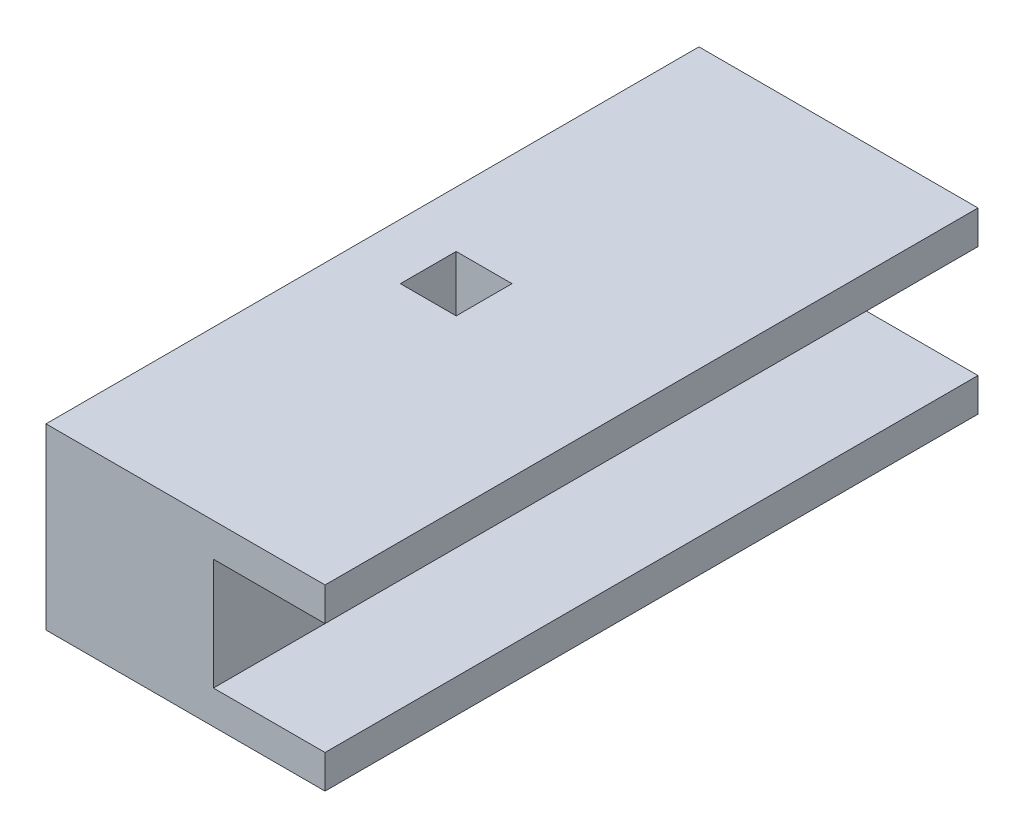
SolidWorks part; units mm, degrees
ref_plane "Płaszczyzna przednia" through (0, 0, 0) normal (0, 0, 1) x (1, 0, 0)
ref_plane "Płaszczyzna górna" through (0, 0, 0) normal (0, 1, 0) x (1, 0, 0)
ref_plane "Płaszczyzna prawa" through (0, 0, 0) normal (1, 0, 0) x (0, 0, -1)
sketch "Szkic1" plane through (0, 0, 0) normal (0, 0, 1) x (1, 0, 0)
  line L0 (10, -10) -> (10, -16)
  line L1 (10, -10) -> (-10, -10)
  line L2 (10, -10) -> (10, 10)
  line L3 (10, 10) -> (-10, 10)
  line L4 (-10, -10) -> (-10, 10)
  line L5 (10, -10) -> (-10, 10) construction
  line L6 (10, 10) -> (-10, -10) construction
  line L7 (10, -16) -> (-40, -16)
  line L8 (-40, -16) -> (-40, 16)
  line L9 (-40, 16) -> (10, 16)
  line L10 (10, 16) -> (10, 10)
  point P0 (0, 0)
  dimension "D1" = 20
  dimension "D2" = 50
  dimension "D3" = 32
  dimension "D4" = 6
extrude "Dodanie-wyciągnięcie1" add sketch "Szkic1" along normal blind 117 contours L10 L9 L8 L7 L0 L1 L4 L3 region at (-20, 0, 0)
sketch "Szkic2" plane through (0, 16, 0) normal (0, 1, 0) x (1, 0, 0)
  line L0 (-40, 0) -> (10, 0) construction
  line L1 (-30, -53.5) -> (-20, -53.5)
  line L2 (-30, -53.5) -> (-30, -63.5)
  line L3 (-30, -63.5) -> (-20, -63.5)
  line L4 (-20, -53.5) -> (-20, -63.5)
  line L5 (-40, -117) -> (-40, 0) construction
  point P4 (-30, -58.5)
  dimension "D1" = 10
  dimension "D2" = 58.5
  dimension "D3" = 10
extrude "Wytnij-wyciągnięcie1" cut sketch "Szkic2" against normal blind 25
sketch "Szkic3" plane through (-10, 0, 0) normal (1, 0, 0) x (0, 0, -1)
  line L0 (-117, 16) -> (0, 16) construction
  circle A0 centre (-58.5, 1) radius 5
  dimension "D1" = 10
  dimension "D2" = 15
extrude "Wytnij-wyciągnięcie2" cut sketch "Szkic3" against normal up to surface (10 mm away) up to face at (-20, 3.5, 58.5)
